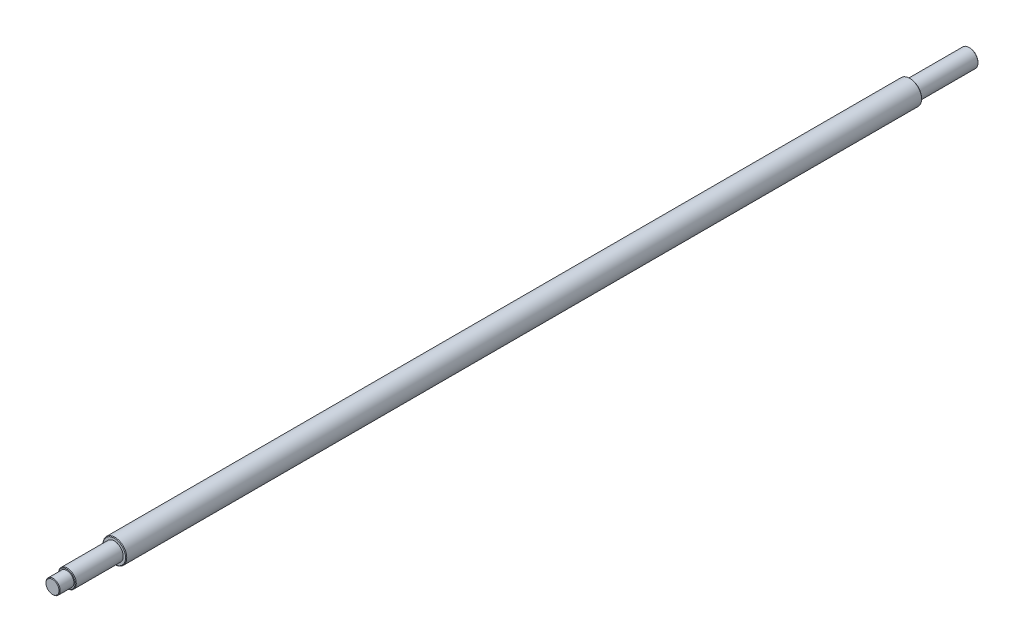
SolidWorks part; units mm, degrees
material "Chrome Stainless Steel"
ref_plane "Front Plane" through (0, 0, 0) normal (0, 0, 1) x (1, 0, 0)
ref_plane "Top Plane" through (0, 0, 0) normal (0, 1, 0) x (1, 0, 0)
ref_plane "Right Plane" through (0, 0, 0) normal (1, 0, 0) x (0, 0, -1)
sketch "Sketch1" plane through (0, 0, 0) normal (0, 0, 1) x (1, 0, 0)
  circle A0 centre (0, 0) radius 10
  dimension "D1" = 20
extrude "Boss-Extrude1" add sketch "Sketch1" along normal mid plane 670
cosmetic thread "Cosmetic Thread1" parameters "D2"=17
sketch "Sketch2" plane through (0, 0, 335) normal (0, 0, 1) x (1, 0, 0)
  circle A0 centre (0, 0) radius 6.4125
  dimension "D1" = 12.825
curve "Helix/Spiral1" pitch 5 height 800 turns 160
sketch "Sketch3" plane through (0, 0, 0) normal (0, 1, 0) x (1, 0, 0)
  circle A0 centre (10, -335) radius 1.5875
  dimension "D1" = 3.175
sweep "Cut-Sweep2" [suppressed] cut profiles "Sketch3" path "Helix/Spiral1"
sketch "Sketch4" plane through (0, 0, 335) normal (0, 0, 1) x (1, 0, 0)
  circle A0 centre (0, 0) radius 7.5
  dimension "D1" = 15
extrude "Boss-Extrude2" add sketch "Sketch4" along normal blind 40
cosmetic thread "Cosmetic Thread2" parameters "D1"=15, "D2"=13
sketch "Sketch5" plane through (0, 0, 375) normal (0, 0, 1) x (1, 0, 0)
  circle A0 centre (0, 0) radius 6
  dimension "D1" = 12
extrude "Boss-Extrude3" add sketch "Sketch5" along normal blind 12
sketch "Sketch6" plane through (0, 0, 375) normal (0, 0, 1) x (1, 0, 0)
  circle A0 centre (0, 0) radius 5.5
  dimension "D1" = 11
curve "Helix/Spiral2" pitch 1 height 12 turns 12
sketch "Sketch7" plane through (0, 0, 0) normal (0, 1, 0) x (1, 0, 0)
  line L0 (7, -375) -> (7.55, -374.6825)
  line L1 (-7.5, -375) -> (7.5, -375) construction
  line L2 (7.5, -375) -> (7.5, -335) construction
  line L3 (7, -375) -> (7.55, -375.3175)
  line L4 (7.55, -375.3175) -> (7.55, -375)
  line L5 (7.55, -375) -> (7.55, -374.6825)
  dimension "D1" = 0.5
  dimension "D2" = 0.55
  dimension "D3" = 60
sweep "Cut-Sweep3" [suppressed] cut profiles "Sketch7" path "Helix/Spiral2"
fillet "Fillet2" [suppressed] radius 0.2
sketch "Sketch8" [suppressed] plane through (0, 0, 0) normal (0, 1, 0) x (1, 0, 0)
  line L3 (7.4, -362.7691) -> (7, -363)
  line L4 (7, -363) -> (7.4, -363.2309)
  line L5 (7.5, -363.4042) -> (7.5, -362.5958)
  line L6 (7.4, -362.7691) -> (7, -363)
  line L7 (7, -363) -> (7.4, -363.2309)
  line L8 (7.5, -363.4042) -> (7.5, -362.5958)
  arc A2 (7.5, -363.4042) -> (7.4, -363.2309) centre (7.2999, -363.4042) ccw
  arc A3 (7.5, -363.4042) -> (7.4, -363.2309) centre (7.2999, -363.4042) ccw
  arc A4 (7.4, -362.7691) -> (7.5, -362.5958) centre (7.2999, -362.5958) ccw
  arc A5 (7.4, -362.7691) -> (7.5, -362.5958) centre (7.2999, -362.5958) ccw
  dimension "D1" = 0
extrude "Cut-Extrude1" [suppressed] cut sketch "Sketch8" against normal through all
sketch "Sketch9" [suppressed] plane through (0, 0, 0) normal (0, -1, 0) x (1, 0, 0)
  line L3 (7.5, 375) -> (7, 375)
  line L4 (7, 375) -> (7.4, 374.7691)
  line L5 (7.5, 374.5958) -> (7.5, 375)
  line L6 (7.5, 375) -> (7, 375)
  line L7 (7, 375) -> (7.4, 374.7691)
  line L8 (7.5, 374.5958) -> (7.5, 375)
  arc A1 (7.5, 374.5958) -> (7.4, 374.7691) centre (7.2999, 374.5958) ccw
  arc A2 (7.5, 374.5958) -> (7.4, 374.7691) centre (7.2999, 374.5958) ccw
  dimension "D1" = 0
extrude "Cut-Extrude2" [suppressed] cut sketch "Sketch9" against normal through all
sketch "Sketch11" plane through (0, 0, -335) normal (0, 0, -1) x (-1, 0, 0)
  circle A0 centre (0, 0) radius 7.5
  dimension "D1" = 15
extrude "Boss-Extrude5" add sketch "Sketch11" along normal blind 50
chamfer "Chamfer2" distance 0.5 angle 45 5 edges at (-7.5, 0, -385) (6, 0, 387) (10, 0, -335) (7.5, 0, 375) (10, 0, 335)
